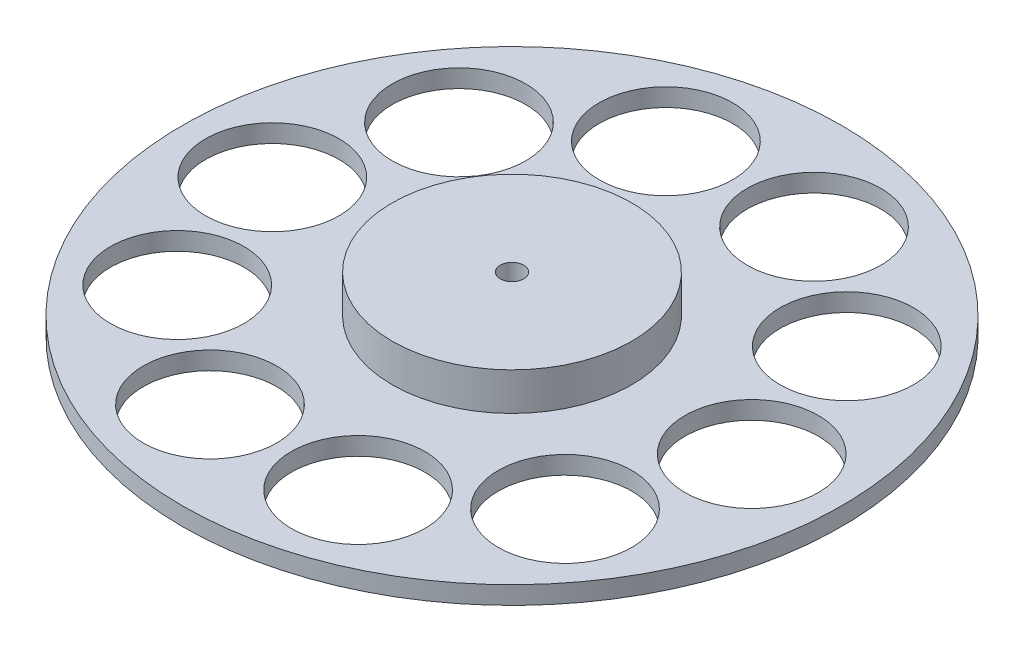
SolidWorks part; units mm, degrees
other "<M28.5x0.6 Tap>-<MinColWidth_OnTracking1>"
ref_plane "Front Plane" through (0, 0, 0) normal (0, 0, 1) x (1, 0, 0)
ref_plane "Top Plane" through (0, 0, 0) normal (0, 1, 0) x (1, 0, 0)
ref_plane "Right Plane" through (0, 0, 0) normal (1, 0, 0) x (0, 0, -1)
sketch "Sketch1" plane through (0, 0, 0) normal (0, 1, 0) x (1, 0, 0)
  circle A9 centre (0, 0) radius 69.85
  dimension "D5" = 139.7
extrude "Boss-Extrude1" add sketch "Sketch1" along normal blind 3.81
ref_plane "Midplane" through (0, 1.905, 0) normal (0, -1, 0) x (-1, 0, 0)
sketch "Sketch4" plane through (0, 3.81, 0) normal (0, 1, 0) x (1, 0, 0)
  circle A1 centre (0, 0) radius 25.4
  dimension "D1" = 50.8
extrude "Boss-Extrude5" add sketch "Sketch4" along normal blind 8
sketch "Sketch25" plane through (0, 0, 0) normal (0, -1, 0) x (1, 0, 0)
  circle A0 centre (0, 0) radius 11.43
  dimension "D1" = 22.86
extrude "Cut-Extrude4" cut sketch "Sketch25" against normal blind 4
sketch "Sketch5" plane through (0, 4, 0) normal (0, 1, 0) x (1, 0, 0)
  circle A5 centre (0, 0) radius 6
  dimension "D1" = 12
extrude "Boss-Extrude6" add sketch "Sketch5" against normal blind 0.508
sketch "Sketch26" plane through (0, 3.492, 0) normal (0, -1, 0) x (1, 0, 0)
  circle A0 centre (0, 0) radius 3.95
  dimension "D1" = 7.9
extrude "Boss-Extrude7" add sketch "Sketch26" along normal blind 5
sketch "Sketch6" plane through (0, 0, 0) normal (0, -1, 0) x (1, 0, 0)
  circle A0 centre (0, 0) radius 2.5
  dimension "D1" = 5
extrude "Cut-Extrude1" cut sketch "Sketch6" against normal through all both and the other way through all
hole_wizard "Tap Drill for M1.2x0.25 Tap1" positions "Sketch13" profile "Sketch14" hole size "M1.2x0.25" standard "ANSI Metric" end condition through all
sketch "Sketch13" plane through (0, 3.81, 0) normal (0, 1, 0) x (1, 0, 0)
  line L0 (0, 0) -> (96.9819, 0) construction
  circle A0 centre (0, 0) radius 69.85 construction
  point P1 (-50.8, 0)
  point P9 (-41.0981, 29.8595)
  point P10 (-15.6981, 48.3137)
  point P11 (15.6981, 48.3137)
  point P12 (41.0981, 29.8595)
  point P13 (50.8, 0)
  point P14 (41.0981, -29.8595)
  point P15 (15.6981, -48.3137)
  point P16 (-15.6981, -48.3137)
  point P17 (-41.0981, -29.8595)
  dimension "D1" = 50.8
  dimension "D2" = 10
sketch "Sketch14" plane through (-50.8, 3.81, 0) normal (1, 0, 0) x (0, 0, 1)
  line L0 (0, 0) -> (0, 5.318)
  line L1 (0, 5.318) -> (14.15, 5.318)
  line L2 (14.15, 5.318) -> (14.15, 0)
  line L5 (14.15, 0) -> (0, 0)
  line L11 (0, -6.35) -> (0, 107.95) construction
  dimension "Thru Hole Dia." = 28.3
  dimension "Thru Hole Depth" = 5.318
ref_axis "Filter axis" through (-41.0981, 0, 29.8595) along (0, 1, 0)
